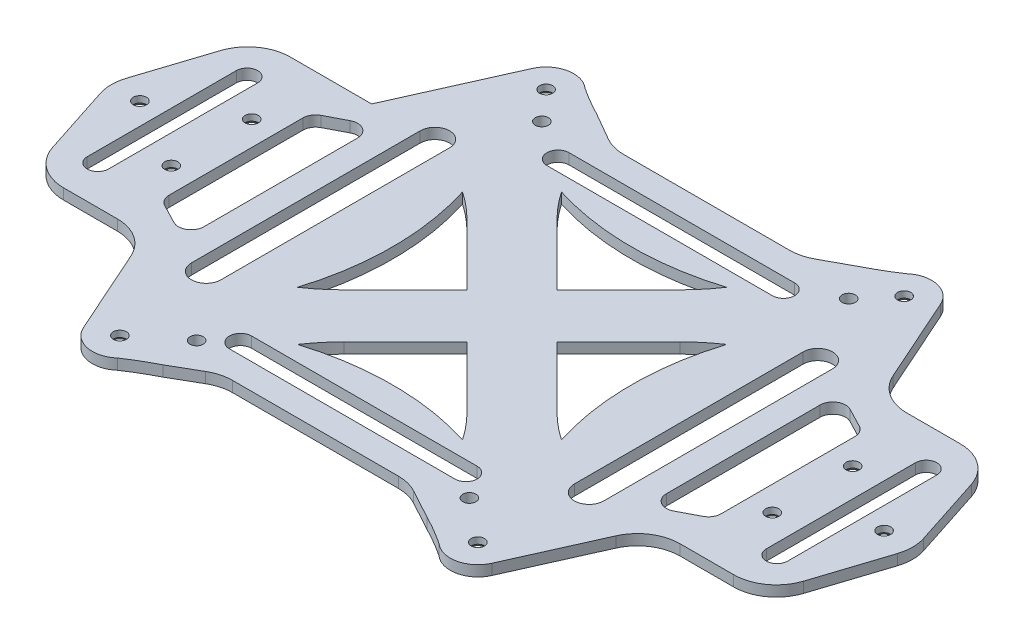
SolidWorks part; units mm, degrees
material "PPS"
ref_plane "前视基准面" through (0, 0, 0) normal (0, 0, 1) x (1, 0, 0)
ref_plane "上视基准面" through (0, 0, 0) normal (0, 1, 0) x (1, 0, 0)
ref_plane "右视基准面" through (0, 0, 0) normal (1, 0, 0) x (0, 0, -1)
sketch "参考" plane through (0, 0, 0) normal (0, 1, 0) x (1, 0, 0)
  line L3 (-133.7177, 0) -> (146.3754, 0) construction
  line L56 (0, 96.0639) -> (0, -115.1457) construction
  line L177 (114.5911, 7.4683) -> (114.5911, -7.4683)
  line L178 (114.5911, 7.4683) -> (43.1936, 17.6463)
  line L179 (114.5911, -7.4683) -> (43.1936, -17.6463)
  line L180 (-114.5911, -7.4683) -> (-43.1936, -17.6463)
  line L181 (-114.5911, 7.4683) -> (-114.5911, -7.4683)
  line L182 (-114.5911, 7.4683) -> (-43.1936, 17.6463)
  arc A18 (-37.7098, 54.831) -> (37.7098, 54.831) centre (0, 111.5317) ccw
  arc A20 (48.2756, 48.4632) -> (43.1936, 17.6463) centre (246.1791, 0) ccw
  arc A21 (48.2756, 48.4632) -> (37.7098, 54.831) centre (42, 50) ccw
  arc A22 (-37.7098, -54.831) -> (37.7098, -54.831) centre (0, -111.5317) cw
  arc A23 (48.2756, -48.4632) -> (43.1936, -17.6463) centre (246.1791, 0) cw
  arc A24 (48.2756, -48.4632) -> (37.7098, -54.831) centre (42, -50) cw
  arc A26 (-48.2756, -48.4632) -> (-37.7098, -54.831) centre (-42, -50) ccw
  arc A27 (-48.2756, -48.4632) -> (-43.1936, -17.6463) centre (-246.1791, 0) ccw
  arc A28 (-48.2756, 48.4632) -> (-37.7098, 54.831) centre (-42, 50) cw
  arc A30 (-48.2756, 48.4632) -> (-43.1936, 17.6463) centre (-246.1791, 0) cw
  dimension "D11" = 50
  dimension "D12" = 42
sketch "草图1" plane through (0, 0, 0) normal (0, 1, 0) x (1, 0, 0)
  line L0 (-160.1541, 0) -> (172.3115, 0) construction
  line L1 (0, 124.2182) -> (0, 50.8906) construction
  line L2 (79.6696, -17.5) -> (79.6696, 17.5) construction
  line L3 (77.1696, -17.5) -> (77.1696, 17.5)
  line L4 (82.1696, -17.5) -> (82.1696, 17.5)
  line L5 (-133.7177, 0) -> (146.3754, 0) construction
  line L6 (47.9, 52.6334) -> (59.525, 26.5883)
  line L7 (59.525, 26.5883) -> (85.8696, 26.5883)
  line L8 (85.8696, 26.5883) -> (94.5058, 0)
  line L9 (59.525, -26.5883) -> (85.8696, -26.5883)
  line L10 (47.9, -52.6334) -> (59.525, -26.5883)
  line L11 (85.8696, -26.5883) -> (94.5058, 0)
  line L12 (-47.9, -52.6334) -> (-59.525, -26.5883)
  line L13 (-59.525, -26.5883) -> (-85.8696, -26.5883)
  line L14 (-85.8696, -26.5883) -> (-94.5058, 0)
  line L15 (-85.8696, 26.5883) -> (-94.5058, 0)
  line L16 (-47.9, 52.6334) -> (-59.525, 26.5883)
  line L17 (-59.525, 26.5883) -> (-85.8696, 26.5883)
  line L18 (-79.6696, -17.5) -> (-79.6696, 17.5) construction
  line L19 (-77.1696, -17.5) -> (-77.1696, 17.5)
  line L20 (-82.1696, -17.5) -> (-82.1696, 17.5)
  line L21 (-24.996, 14.4296) -> (-10.5664, 0)
  line L22 (14.4296, 24.996) -> (0, 10.5664)
  line L23 (-24.996, -14.4296) -> (-10.5664, 0)
  line L24 (-14.4296, 24.996) -> (0, 10.5664)
  line L25 (0, 96.0639) -> (0, -115.1457) construction
  line L26 (24.996, -14.4296) -> (10.5664, 0)
  line L27 (24.996, 14.4296) -> (10.5664, 0)
  line L28 (-14.4296, -24.996) -> (0, -10.5664)
  line L29 (14.4296, -24.996) -> (0, -10.5664)
  line L30 (44.9192, -26.8293) -> (44.9192, 26.8293) construction
  line L31 (41.4687, -26.8293) -> (41.4687, 26.8293)
  line L32 (48.3697, -26.8293) -> (48.3697, 26.8293)
  line L33 (-26.4535, -37.2441) -> (26.4535, -37.2441) construction
  line L34 (-26.4535, -34.637) -> (26.4535, -34.637)
  line L35 (-26.4535, -39.8513) -> (26.4535, -39.8513)
  line L36 (-26.4535, 37.2441) -> (26.4535, 37.2441) construction
  line L37 (-26.4535, 34.637) -> (26.4535, 34.637)
  line L38 (-26.4535, 39.8513) -> (26.4535, 39.8513)
  line L39 (-44.9192, -26.8293) -> (-44.9192, 26.8293) construction
  line L40 (-41.4687, -26.8293) -> (-41.4687, 26.8293)
  line L41 (-48.3697, -26.8293) -> (-48.3697, 26.8293)
  line L44 (0, -45.8906) -> (21.7864, -45.8906)
  line L45 (21.7864, -45.8906) -> (30.9782, -50.8906)
  line L46 (0, -45.8906) -> (-22.3179, -45.8906)
  line L47 (-22.3179, -45.8906) -> (-30.9782, -50.8906)
  line L48 (0, -50.8906) -> (0, -143.4382) construction
  line L49 (21.7864, 45.8906) -> (30.9782, 50.8906)
  line L50 (0, 45.8906) -> (21.7864, 45.8906)
  line L51 (0, 45.8906) -> (-22.3179, 45.8906)
  line L52 (-22.3179, 45.8906) -> (-30.9782, 50.8906)
  line L53 (0, 45.8906) -> (0, -45.8906) construction
  circle A6 centre (42, 50) radius 1.55
  circle A7 centre (42, -50) radius 1.55
  circle A8 centre (-42, -50) radius 1.55
  circle A9 centre (-42, 50) radius 1.55
  circle A10 centre (36, 43) radius 1.55
  circle A11 centre (32, -42) radius 1.55
  circle A12 centre (-32, -42) radius 1.55
  circle A13 centre (-36, 43) radius 1.55
  arc A14 (47.9, 52.6334) -> (37.7098, 54.831) centre (42, 50) ccw
  arc A15 (-37.7098, 54.831) -> (-30.9782, 50.8906) centre (0, 111.5317) ccw
  arc A18 (77.1696, -17.5) -> (82.1696, -17.5) centre (79.6696, -17.5) ccw
  arc A19 (82.1696, 17.5) -> (77.1696, 17.5) centre (79.6696, 17.5) ccw
  circle A20 centre (70.5, 9.4358) radius 1.55
  circle A21 centre (70.5, -9.4358) radius 1.55
  circle A22 centre (-70.5, -9.4358) radius 1.55
  circle A23 centre (-70.5, 9.4358) radius 1.55
  circle A24 centre (87.3, 0) radius 1.55
  arc A25 (48.2756, 48.4632) -> (37.7098, 54.831) centre (42, 50) ccw construction
  arc A26 (47.9, -52.6334) -> (37.7098, -54.831) centre (42, -50) cw
  arc A27 (-37.7098, -54.831) -> (-30.9782, -50.8906) centre (0, -111.5317) cw
  arc A28 (-47.9, 52.6334) -> (-37.7098, 54.831) centre (-42, 50) cw
  arc A29 (-77.1696, -17.5) -> (-82.1696, -17.5) centre (-79.6696, -17.5) cw
  arc A30 (-82.1696, 17.5) -> (-77.1696, 17.5) centre (-79.6696, 17.5) cw
  circle A31 centre (-87.3, 0) radius 1.55
  arc A32 (-47.9, -52.6334) -> (-37.7098, -54.831) centre (-42, -50) ccw
  arc A33 (-24.996, 14.4296) -> (-30.9782, 19.3706) centre (-53.9062, -14.4807) ccw
  arc A34 (-24.996, -14.4296) -> (-30.9782, -19.3706) centre (-53.9062, 14.4807) cw
  arc A35 (-30.9782, -19.3706) -> (-30.9782, 19.3706) centre (-93.0146, 0) ccw
  arc A36 (-14.4296, 24.996) -> (-19.3706, 30.9782) centre (14.4807, 53.9062) cw
  arc A37 (-19.3706, 30.9782) -> (19.3706, 30.9782) centre (0, 93.0146) ccw
  arc A38 (14.4296, 24.996) -> (19.3706, 30.9782) centre (-14.4807, 53.9062) ccw
  arc A39 (24.996, 14.4296) -> (30.9782, 19.3706) centre (53.9062, -14.4807) cw
  arc A40 (30.9782, 19.3706) -> (30.9782, -19.3706) centre (93.0146, 0) ccw
  arc A41 (24.996, -14.4296) -> (30.9782, -19.3706) centre (53.9062, 14.4807) ccw
  arc A42 (14.4296, -24.996) -> (19.3706, -30.9782) centre (-14.4807, -53.9062) cw
  arc A43 (19.3706, -30.9782) -> (-19.3706, -30.9782) centre (0, -93.0146) ccw
  arc A44 (-14.4296, -24.996) -> (-19.3706, -30.9782) centre (14.4807, -53.9062) ccw
  arc A45 (41.4687, -26.8293) -> (48.3697, -26.8293) centre (44.9192, -26.8293) ccw
  arc A46 (48.3697, 26.8293) -> (41.4687, 26.8293) centre (44.9192, 26.8293) ccw
  arc A47 (-26.4535, -34.637) -> (-26.4535, -39.8513) centre (-26.4535, -37.2441) ccw
  arc A48 (26.4535, -39.8513) -> (26.4535, -34.637) centre (26.4535, -37.2441) ccw
  arc A49 (-26.4535, 34.637) -> (-26.4535, 39.8513) centre (-26.4535, 37.2441) cw
  arc A50 (26.4535, 39.8513) -> (26.4535, 34.637) centre (26.4535, 37.2441) cw
  arc A51 (-41.4687, -26.8293) -> (-48.3697, -26.8293) centre (-44.9192, -26.8293) cw
  arc A52 (-48.3697, 26.8293) -> (-41.4687, 26.8293) centre (-44.9192, 26.8293) cw
  arc A53 (30.9782, 50.8906) -> (37.7098, 54.831) centre (0, 111.5317) ccw
  arc A54 (30.9782, -50.8906) -> (37.7098, -54.831) centre (0, -111.5317) cw
  point P30 (79.6696, 0)
  point P63 (44.9192, 0)
  point P78 (-79.6696, 0)
  point P98 (0, 0)
  point P116 (0, -37.2441)
  point P129 (0, 37.2441)
  point P136 (-44.9192, 0)
  dimension "D1" = 50
  dimension "D3" = 3.1
  dimension "D8" = 2.5
  dimension "D10" = 3.1
  dimension "D12" = 3.1
  dimension "D2" = 42
  dimension "D4" = 36
  dimension "D5" = 32
  dimension "D6" = 42
  dimension "D7" = 43
  dimension "D9" = 35
  dimension "D11" = 70.5
  dimension "D13" = 87.3
  dimension "D14" = 4
extrude "凸台-拉伸1" add sketch "草图1" along normal blind 2.5
chamfer "倒角2" distance 1 angle 45 10 edges at (-70.5, 0, 10.9858) (-70.5, 0, -10.9858) (70.5, 0, 7.8858) (70.5, 0, -7.8858) (-87.3, 0, -1.55) (87.3, 0, 1.55) (-42, 0, 51.55) (42, 0, 48.45) (-42, 0, -51.55) (42, 0, -48.45)
sketch "减重草图镂空-如果影响结构强度则取消" plane through (0, 0, 0) normal (0, -1, 0) x (1, 0, 0)
  line L0 (0, 0) -> (0, 77.9145) construction
  line L1 (0, 0) -> (127.571, 0) construction
  line L2 (-64.75, 17.5) -> (-54.25, 22.966)
  line L3 (-54.25, 22.966) -> (-54.25, -22.966)
  line L4 (-54.25, -22.966) -> (-64.75, -17.5)
  line L5 (-64.75, -17.5) -> (-64.75, 17.5)
  line L6 (54.25, -22.966) -> (64.75, -17.5)
  line L7 (54.25, 22.966) -> (54.25, -22.966)
  line L8 (64.75, 17.5) -> (54.25, 22.966)
  line L9 (64.75, -17.5) -> (64.75, 17.5)
  circle A1 centre (-70.5, 9.4358) radius 1.55 construction
  dimension "D1" = 5.75
  dimension "D2" = 54.25
  dimension "D3" = 62.5
  dimension "D4" = 17.5
extrude "减重-如果影响结构强度则取消" cut sketch "减重草图镂空-如果影响结构强度则取消" against normal through all
fillet "圆角2" radius 3 8 edges at (64.75, 1.25, 17.5) (64.75, 1.25, -17.5) (54.25, 1.25, -22.966) (54.25, 1.25, 22.966) (-54.25, 1.25, -22.966) (-64.75, 1.25, -17.5) (-64.75, 1.25, 17.5) (-54.25, 1.25, 22.966)
fillet "圆角3" radius 10 13 edges at (21.7864, 1.25, 45.8906) (-22.3179, 1.25, 45.8906) (21.7864, 1.25, -45.8906) (-22.3179, 1.25, -45.8906) (59.525, 1.25, -26.5883) (85.8696, 1.25, -26.5883) (94.5058, 1.25, 0) (85.8696, 1.25, 26.5883) (59.525, 1.25, 26.5883) (-59.525, 1.25, 26.5883) (-85.8696, 1.25, -26.5883) (-94.5058, 1.25, 0) (-85.8696, 1.25, 26.5883)
